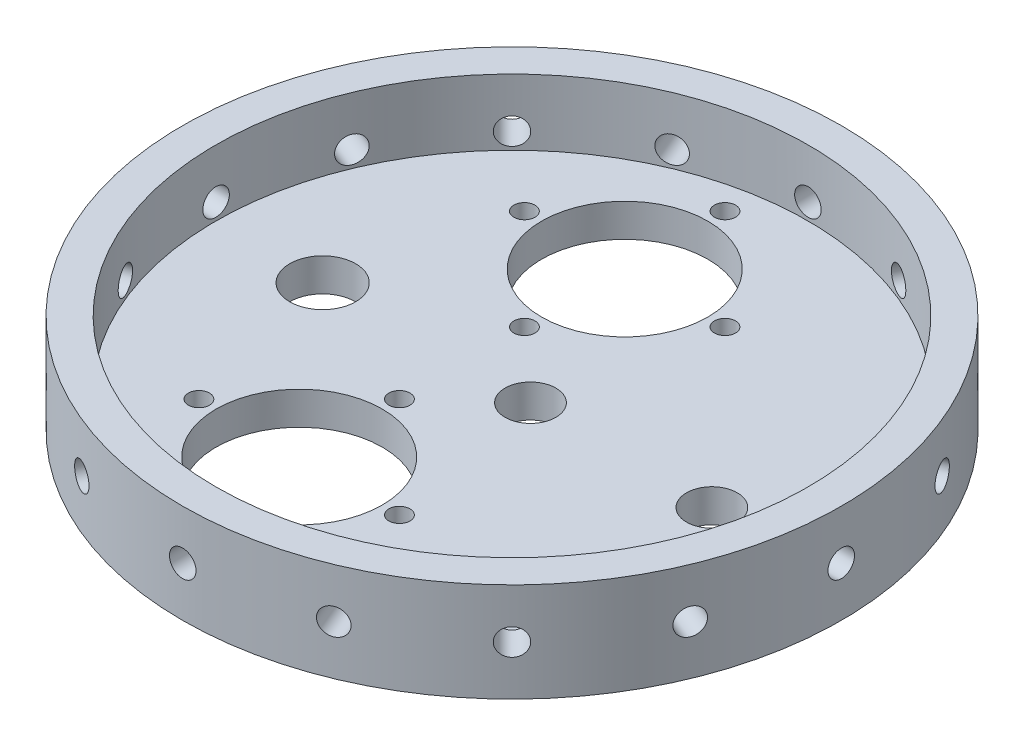
SolidWorks part; units mm, degrees
material "AISI 1020"
ref_plane "Front Plane" through (0, 0, 0) normal (0, 0, 1) x (1, 0, 0)
ref_plane "Top Plane" through (0, 0, 0) normal (0, 1, 0) x (1, 0, 0)
ref_plane "Right Plane" through (0, 0, 0) normal (1, 0, 0) x (0, 0, -1)
ref_axis "Longitudinal Axis" through (0, 0, 0) along (0, 1, 0)
sketch "Sketch1" plane through (0, 0, 0) normal (0, 1, 0) x (1, 0, 0)
  circle A0 centre (0, 0) radius 63.4365
  dimension "D1" = 126.873
extrude "Boss-Extrude4" add sketch "Sketch1" along normal blind 6.35
ref_plane "Plane1" through (-63.4365, 0, 0) normal (-1, 0, 0) x (0, 0, 1)
sketch "Sketch25" plane through (0, 0, 0) normal (0, -1, 0) x (1, 0, 0)
  line L0 (0, 0) -> (63.373, 0)
  line L1 (63.373, 0) -> (-63.373, 0)
  line L2 (-63.373, 0) -> (-9.525, 0)
  circle A2 centre (-36.449, 0) radius 6.35
  dimension "D1" = 12.7
extrude "Cut-Extrude6" cut sketch "Sketch25" against normal blind 65.786 contours A2
ref_plane "Plane2" through (0, 0, 63.5) normal (0, 0, 1) x (1, 0, 0)
sketch "Sketch32" plane through (0, 6.35, 0) normal (0, 1, 0) x (1, 0, 0)
  circle A0 centre (0, 0) radius 57.023
  circle M29 centre (0, 0) radius 63.4365
extrude "Boss-Extrude3" add sketch "Sketch32" along normal blind 12.7 contours A0 M29 region at (-61.6422, 6.35, 0)
sketch "Sketch33" plane through (0, 0, 63.5) normal (0, 0, 1) x (1, 0, 0)
  line L2 (-63.4365, 0) -> (63.4365, 0) construction
  point P0 (0, 9.525)
  dimension "D1" = 9.525
hole_wizard "Tap Drill for 1/4-20 Tap1" positions "Sketch34" profile "Sketch36" hole size "1/4-20" standard "ANSI Inch"
sketch "Sketch34" plane through (0, 0, 63.5) normal (0, 0, 1) x (1, 0, 0)
  point P0 (0, 9.525)
sketch "Sketch36" plane through (0, 9.525, 63.5) normal (1, 0, 0) x (0, -1, 0)
  line L0 (0, 0) -> (0, 11.0588)
  line L1 (0, 11.0588) -> (2.5527, 9.525)
  line L2 (2.5527, 9.525) -> (2.5527, 0)
  line L5 (2.5527, 0) -> (0, 0)
  line L10 (0, 11.0588) -> (-2.5527, 9.525) construction
  line L11 (0, -6.35) -> (0, 107.95) construction
  dimension "Hole Dia." = 5.1054
  dimension "Hole Depth" = 9.525
  dimension "Drill Angle" = 118
pattern_circular "CirPattern7" count 16 over 360 about axis through (0, 0, 0) along (0, 1, 0) of "Tap Drill for 1/4-20 Tap1"
sketch "Sketch59" plane through (0, 0, 0) normal (0, -1, 0) x (1, 0, 0)
  line L2 (-9.652, 31.3191) -> (-28.956, 31.3191)
  line L3 (-28.956, 31.3191) -> (-9.652, 31.3191)
  line L4 (-9.652, -31.349) -> (9.652, -31.349)
  line L5 (9.652, -31.349) -> (-9.652, -31.349)
  line L6 (-9.652, -31.349) -> (-28.956, -31.349)
  line L7 (-9.652, 31.3191) -> (9.652, 31.3191)
  circle A0 centre (-9.652, 31.3191) radius 16.002
  circle A1 centre (-9.652, -31.349) radius 16.002
  circle A2 centre (-9.652, 31.3191) radius 19.304
  circle A3 centre (-9.652, -31.349) radius 19.304
  circle A4 centre (-9.652, 50.6231) radius 2.032
  circle A5 centre (9.652, 31.3191) radius 2.032
  circle A6 centre (-9.652, 12.0151) radius 2.032
  circle A7 centre (-28.956, 31.3191) radius 2.032
  circle A8 centre (-9.652, -12.045) radius 2.032
  circle A9 centre (9.652, -31.349) radius 2.032
  circle A10 centre (-9.652, -50.653) radius 2.032
  circle A11 centre (-28.956, -31.349) radius 2.032
  dimension "D1" = 32.004
  dimension "D2" = 32.004
  dimension "D3" = 38.608
  dimension "D4" = 38.608
  dimension "D5" = 4.064
  dimension "D6" = 4.064
  dimension "D7" = 4.064
  dimension "D8" = 4.064
  dimension "D9" = 4.064
  dimension "D10" = 4.064
  dimension "D11" = 4.064
  dimension "D12" = 4.064
extrude "Cut-Extrude10" cut sketch "Sketch59" against normal blind 80.518 contours A4 | A5 | A6 | A7 | A8 | A9 | A10 | A11 | A1 | A0
sketch "Sketch62" plane through (0, 0, 0) normal (0, -1, 0) x (1, 0, 0)
  line L0 (-42.799, 0) -> (63.4365, 0)
  line L1 (0, 0) -> (63.4365, 0) construction
  line L2 (0, 0) -> (63.4365, 0) construction
  line L3 (31.7182, 0) -> (10.3188, 0) construction
  circle A0 centre (-36.449, 0) radius 6.35 construction
  circle A1 centre (0, 0) radius 63.4365 construction
  circle A2 centre (21.0185, 0) radius 17.4625
  circle A3 centre (3.556, 0) radius 4.8895
  circle A4 centre (38.481, 0) radius 4.8895
  dimension "D1" = 34.925
  dimension "D2" = 9.779
  dimension "D3" = 9.779
extrude "Cut-Extrude12" cut sketch "Sketch62" against normal blind 80.518 contours A3 | A4
